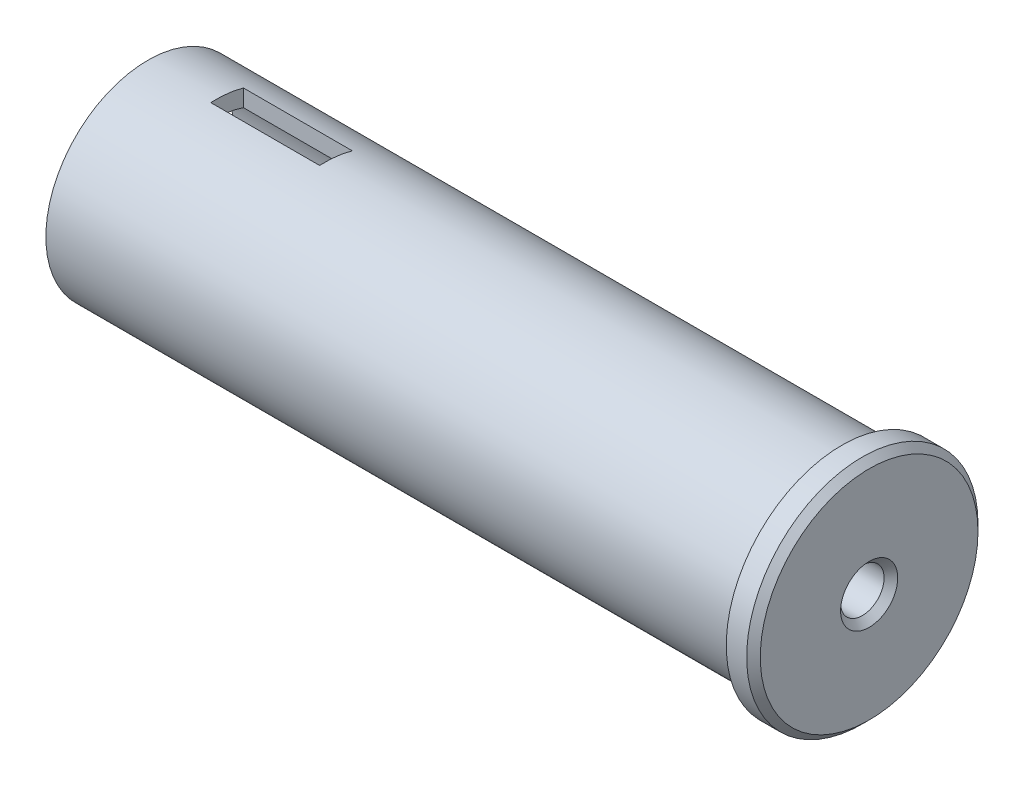
SolidWorks part; units mm, degrees
material "Custom Plastic"
ref_plane "Front Plane" through (0, 0, 0) normal (0, 0, 1) x (1, 0, 0)
ref_plane "Top Plane" through (0, 0, 0) normal (0, 1, 0) x (1, 0, 0)
ref_plane "Right Plane" through (0, 0, 0) normal (1, 0, 0) x (0, 0, -1)
sketch "Sketch2" plane through (0, 0, 0) normal (0, 1, 0) x (1, 0, 0)
  line L0 (0, 0) -> (-62.0809, 0) construction
  line L1 (0, 1.6) -> (-11, 1.6)
  line L2 (-11, 1.6) -> (-11, 6.3)
  line L3 (-11, 6.3) -> (-53, 6.3)
  line L7 (-53, 7.5) -> (-2, 7.5)
  line L8 (-2, 7.5) -> (-2, 8.5)
  line L9 (-2, 8.5) -> (0, 8.5)
  line L10 (0, 8.5) -> (0, 1.6)
  line L11 (-53, 7.5) -> (-53, 6.3)
  dimension "D1" = 3.2
  dimension "D2" = 15
  dimension "D3" = 1.2
  dimension "D4" = 2
  dimension "D5" = 1
  dimension "D6" = 51
  dimension "D7" = 11
revolve "Revolve1" add sketch "Sketch2" angle 360 about L0
chamfer "Chamfer2" distance 0.5 angle 45 2 edges at (0, 0, -1.6) (0, 0, -8.5)
sketch "Sketch3" plane through (0, 0, 0) normal (0, 1, 0) x (1, 0, 0)
  line L0 (-53, 7.5) -> (-53, -7.5) construction
  line L1 (-40, 2.0171) -> (-48, 2.0171)
  line L2 (-40, 2.0171) -> (-40, -0.3829)
  line L3 (-40, -0.3829) -> (-48, -0.3829)
  line L4 (-48, 2.0171) -> (-48, -0.3829)
  line L5 (-40, 2.0171) -> (-48, -0.3829) construction
  line L6 (-40, -0.3829) -> (-48, 2.0171) construction
  point P0 (-44, 0.8171)
  dimension "D1" = 2.4
  dimension "D2" = 8
  dimension "D3" = 5
extrude "Cut-Extrude1" cut sketch "Sketch3" against normal through all and the other way through all
